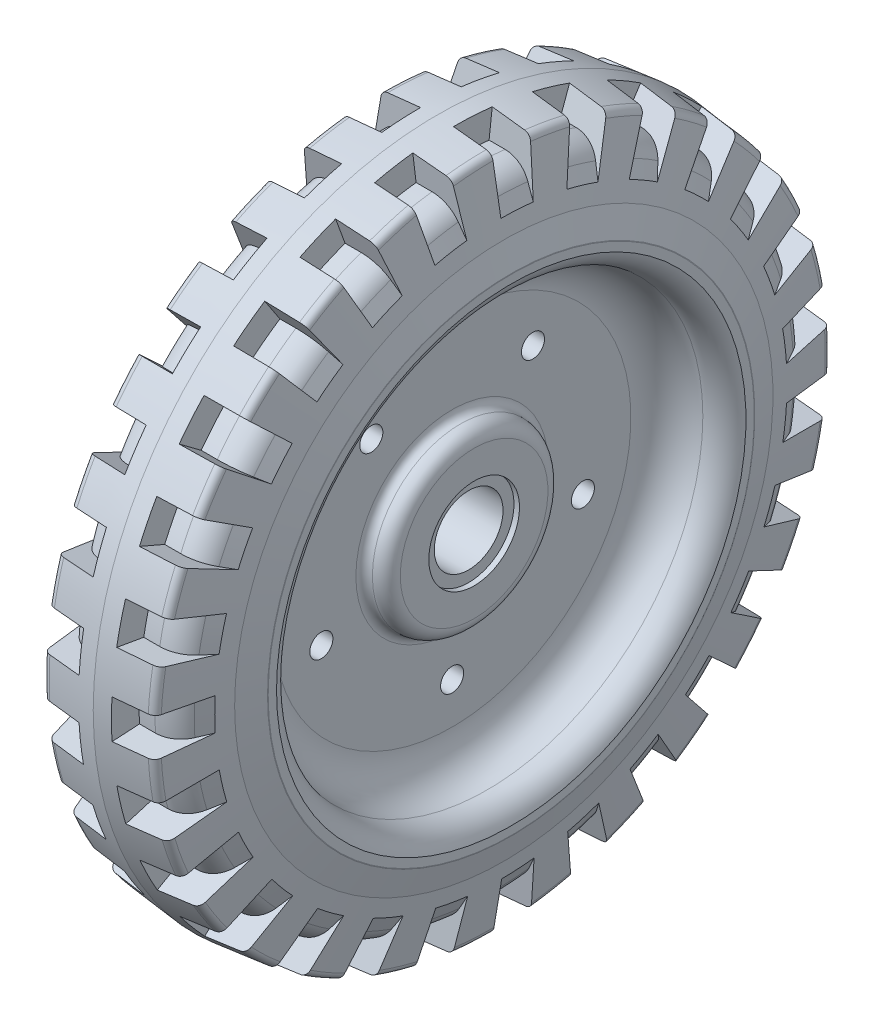
SolidWorks part; units mm, degrees
material "POLYURETHANE (11671)"
ref_plane "Front Plane" through (0, 0, 0) normal (0, 0, 1) x (1, 0, 0)
ref_plane "Top Plane" through (0, 0, 0) normal (0, 1, 0) x (1, 0, 0)
ref_plane "Right Plane" through (0, 0, 0) normal (1, 0, 0) x (0, 0, -1)
sketch "Sketch1" plane through (0, 0, 0) normal (0, 0, 1) x (1, 0, 0)
  line L0 (-13.5, 0) -> (13.5, 0) construction
  line L1 (13.5, 12.5) -> (13.5, 25)
  line L3 (13.5, 25) -> (13.5, 26.8406)
  line L4 (8.3406, 32) -> (8.5, 32)
  line L5 (5.5, 35) -> (5.5, 65)
  line L7 (27.5, 88.4875) -> (27.5, 84.4165)
  line L8 (27.5, 84.4165) -> (26.992, 84.4165)
  line L9 (26.992, 84.4165) -> (26.992, 88.3684)
  line L10 (24.2871, 97.8656) -> (26.961, 88.5882)
  line L11 (24.2871, 97.8656) -> (20.355, 120.7956)
  line L12 (17.9116, 123.0885) -> (0, 125)
  line L13 (0, 0) -> (0, 125) construction
  line L14 (13.5, 12.5) -> (-13.5, 12.5)
  line L15 (13.5, 0) -> (13.5, 12.5) construction
  line L16 (-13.5, 0) -> (-13.5, 12.5) construction
  line L17 (-17.9116, 123.0885) -> (0, 125)
  line L18 (-24.2871, 97.8656) -> (-20.355, 120.7956)
  line L19 (-24.2871, 97.8656) -> (-26.961, 88.5882)
  line L20 (-26.992, 84.4165) -> (-26.992, 88.3684)
  line L22 (-27.5, 88.4875) -> (-27.5, 84.4165)
  line L24 (-5.5, 35) -> (-5.5, 65)
  line L25 (-8.3406, 32) -> (-8.5, 32)
  line L26 (-13.5, 25) -> (-13.5, 26.8406)
  line L28 (-13.5, 12.5) -> (-13.5, 25)
  arc A0 (8.3406, 32) -> (13.5, 26.8406) centre (8.3406, 26.8406) cw
  arc A1 (8.5, 32) -> (5.5, 35) centre (8.5, 35) cw
  arc A2 (18.1533, 78.5089) -> (5.5, 65) centre (19.0378, 65) ccw
  arc A3 (17.9116, 123.0885) -> (20.355, 120.7956) centre (17.6168, 120.326) cw
  arc A4 (26.961, 88.5882) -> (26.992, 88.3684) centre (26.1982, 88.3684) cw
  arc A5 (27.5, 88.4875) -> (18.1533, 78.5089) centre (17.5, 88.4875) cw
  arc A6 (-27.5, 88.4875) -> (-18.1533, 78.5089) centre (-17.5, 88.4875) ccw
  arc A7 (-26.961, 88.5882) -> (-26.992, 88.3684) centre (-26.1982, 88.3684) ccw
  arc A8 (-17.9116, 123.0885) -> (-20.355, 120.7956) centre (-17.6168, 120.326) ccw
  arc A9 (-18.1533, 78.5089) -> (-5.5, 65) centre (-19.0378, 65) cw
  arc A10 (-8.5, 32) -> (-5.5, 35) centre (-8.5, 35) ccw
  arc A11 (-8.3406, 32) -> (-13.5, 26.8406) centre (-8.3406, 26.8406) ccw
  point P19 (27.5, 75.2924)
  point P30 (13.5, 32)
  point P33 (5.5, 32)
  point P39 (20, 122.8656)
  point P42 (26.992, 88.4805)
  point P56 (0, 12.5)
  point P61 (-26.992, 88.4805)
  point P62 (-20, 122.8656)
  point P63 (-5.5, 32)
  point P64 (-13.5, 32)
  point P65 (-27.5, 75.2924)
  dimension "D16" = 5.1594
  dimension "D17" = 3
  dimension "D18" = 65
  dimension "D20" = 2.7781
  dimension "D21" = 0.7937
  dimension "D23" = 10
  dimension "D1" = 13.5
  dimension "D3" = 8
  dimension "D4" = 55
  dimension "D5" = 0.508
  dimension "D7" = 20
  dimension "D8" = 12.5
  dimension "D9" = 25
  dimension "D10" = 35
  dimension "D11" = 9.1241
  dimension "D13" = 4.064
  dimension "D15" = 25
  dimension "D19" = 125
  dimension "D22" = 1.9115
revolve "Revolve2" add sketch "Sketch1" angle 360 about L0 region at (0, 80.0289, 0)
sketch "Sketch5" plane through (5.5, 0, 0) normal (1, 0, 0) x (0, 0, -1)
  point P0 (0, -50)
  dimension "D1" = 50
hole_wizard "M8 Clearance Hole1" positions "3DSketch1" profile "Sketch6" hole size "M8" standard "ISO" end condition up to next
sketch3d "3DSketch1"
  point P0 (5.5, -50, 0)
sketch "Sketch6" plane through (5.5, -50, 0) normal (0, 1, 0) x (0, 0, -1)
  line L0 (0, 0) -> (0, 11)
  line L1 (0, 11) -> (4.2, 11)
  line L2 (4.2, 11) -> (4.2, 0)
  line L5 (4.2, 0) -> (0, 0)
  line L11 (0, -6.35) -> (0, 107.95) construction
  dimension "Thru Hole Dia." = 8.4
  dimension "Thru Hole Depth" = 11
pattern_circular "CirPattern1" count 5 over 360 about axis through (24.2871, 0, 0) along (-1, 0, 0) of "M8 Clearance Hole1"
sketch "Sketch7" plane through (0, 0, 0) normal (0, 0, 1) x (1, 0, 0)
  line L0 (23.2285, 104.0391) -> (20.704, 108.9394)
  line L2 (17.9116, 123.0885) -> (17.9116, -123.0885) construction
  line L3 (11.8143, 114.3597) -> (6, 114.3597)
  line L4 (0, 0) -> (0, 122.4189) construction
  line L5 (0, 125) -> (0, -125) construction
  line L6 (6, 114.3597) -> (6, 124.3597)
  line L7 (17.9116, 123.0885) -> (0, 125) construction
  line L8 (24.2871, 97.8656) -> (20.355, 120.7956) construction
  line L9 (17.9116, 123.0885) -> (6, 124.3597)
  line L10 (24.2871, 97.8656) -> (20.355, 120.7956)
  line L11 (-24.2871, 97.8656) -> (-20.355, 120.7956)
  line L12 (-17.9116, 123.0885) -> (-6, 124.3597)
  line L13 (-6, 114.3597) -> (-6, 124.3597)
  line L14 (-11.8143, 114.3597) -> (-6, 114.3597)
  line L15 (-23.2285, 104.0391) -> (-20.704, 108.9394)
  arc A0 (20.355, 120.7956) -> (17.9116, 123.0885) centre (17.6168, 120.326) ccw construction
  arc A1 (20.355, 120.7956) -> (17.9116, 123.0885) centre (17.6168, 120.326) ccw
  arc A2 (20.704, 108.9394) -> (11.8143, 114.3597) centre (11.8143, 104.3597) ccw
  arc A3 (-20.704, 108.9394) -> (-11.8143, 114.3597) centre (-11.8143, 104.3597) cw
  arc A4 (-20.355, 120.7956) -> (-17.9116, 123.0885) centre (-17.6168, 120.326) cw
  point P3 (17.9116, 114.3597)
  point P28 (-17.9116, 114.3597)
  dimension "D2" = 10
  dimension "D1" = 6
  dimension "D3" = 10
ref_axis "Axis1" through (13.5, 0, 0) along (-1, 0, 0)
revolve "Cut-Revolve1" cut sketch "Sketch7" angle 6.5 about axis through (13.5, 0, 0) along (-1, 0, 0) region at (14.1709, 117.7552, 0)
pattern_circular "CirPattern2" count 27 over 360 about axis through (13.5, 0, 0) along (-1, 0, 0) of "Cut-Revolve1"
revolve "Cut-Revolve2" cut sketch "Sketch7<5>" angle 6.5 about axis through (13.5, 0, 0) along (-1, 0, 0) region at (-14.1709, 117.7552, 0) reverse direction yes
sketch "Sketch7<5>" plane through (0, 0, 0) normal (0, 0, 1) x (1, 0, 0) same geometry as "Sketch7"
pattern_circular "CirPattern3" count 27 over 360 about axis through (13.5, 0, 0) along (-1, 0, 0) of "Cut-Revolve2"
sketch "Sketch8" plane through (13.5, 0, 0) normal (1, 0, 0) x (0, 0, -1)
  circle A0 centre (0, 0) radius 16.5
  circle A1 centre (0, 0) radius 12.5 construction
  circle A2 centre (0, 0) radius 12.5
  dimension "D1" = 33
extrude "Cut-Extrude1" cut sketch "Sketch8" against normal blind 2
mirror "Mirror1" about plane through (0, 0, 0) normal (1, 0, 0) of "Cut-Extrude1"
